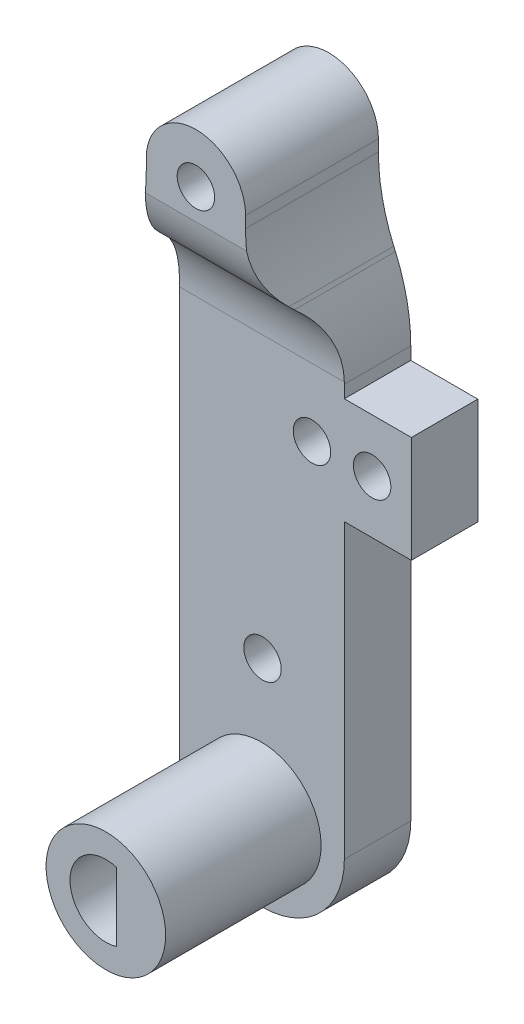
SolidWorks part; units mm, degrees
ref_plane "Front Plane" through (0, 0, 0) normal (0, 0, 1) x (1, 0, 0)
ref_plane "Top Plane" through (0, 0, 0) normal (0, 1, 0) x (1, 0, 0)
ref_plane "Right Plane" through (0, 0, 0) normal (1, 0, 0) x (0, 0, -1)
sketch "Sketch1" plane through (0, 0, 0) normal (0, 0, 1) x (1, 0, 0)
  line L0 (-5.898, 28.3342) -> (-5.898, 27.2476)
  line L1 (-2.8056, 11.5313) -> (-2.8056, 12.738)
  line L2 (3.6016, 11.5313) -> (3.6016, 1.3594)
  line L3 (-18.5662, 11.5313) -> (-18.5662, -26.5933)
  line L4 (3.6016, 1.3594) -> (-2.8056, 1.3594)
  line L5 (-2.8056, -26.5933) -> (-2.8056, 1.3594)
  line L6 (3.6016, 11.5313) -> (-2.8056, 11.5313)
  line L7 (-16.8793, 20.1661) -> (-17.0781, 19.7113)
  line L8 (-2.8056, 11.5313) -> (-18.5662, 11.5313) construction
  line L9 (-18.5662, 11.5313) -> (-18.5662, 12.5907)
  line L10 (-15.3912, 28.3342) -> (-15.3912, 27.2867)
  line L11 (-10.6859, -34.4736) -> (-36.5829, -34.4736) construction
  line L12 (-4.2728, 19.8107) -> (-4.4307, 20.1749)
  circle A0 centre (-10.6446, 28.3342) radius 1.7907
  circle A1 centre (-0.1512, 6.4513) radius 1.7907
  circle A2 centre (-5.898, 6.4513) radius 1.7907
  circle A3 centre (-10.6446, 28.3342) radius 4.7466
  circle A4 centre (-10.6859, -26.5933) radius 7.8803
  arc A5 (-18.5662, 12.5907) -> (-17.0781, 19.7113) centre (-0.7862, 12.5907) cw
  arc A6 (-15.3912, 27.2867) -> (-16.8793, 20.1661) centre (-33.1712, 27.2867) cw
  arc A7 (-5.898, 27.2476) -> (-4.4307, 20.1749) centre (11.882, 27.2476) ccw
  arc A8 (-2.8056, 12.738) -> (-4.2728, 19.8107) centre (-20.5856, 12.738) ccw
  circle A9 centre (-10.6287, -13.8687) radius 1.7907
  dimension "D1" = 17.78
  dimension "D2" = 3.5814
  dimension "D3" = 15.7606
  dimension "D4" = 3.5814
  dimension "D5" = 3.5814
  dimension "D6" = 7.9375
  dimension "D7" = 20.32
  dimension "D8" = 5.08
extrude "Boss-Extrude1" add sketch "Sketch1" along normal blind 12.7 contours A4 | L6 L8 L3 A4 L5 L4 L2 A2 A1 A9 | L8 L1 A8 L12 A7 L0 A3 L10 A6 L7 A5 L9 | A3 A0 region at (-10.6446, 23.7219, 0) region at (-9.8877, 1.7898, 0) region at (-10.6859, -26.5933, 0)
ref_plane "Plane2" through (0, -34.4736, 0) normal (0, -1, 0) x (-1, 0, 0)
sketch "Sketch5" plane through (-18.5662, 0, 0) normal (-1, 0, 0) x (0, 0, 1)
  line L0 (6.35, -34.4736) -> (12.7, -34.4736)
  line L1 (12.7, -34.4736) -> (12.7, 27.6449)
  line L2 (-6.35, -34.4736) -> (-12.7, -34.4736)
  line L3 (-12.7, -34.4736) -> (-12.7, 27.6449)
  line L4 (-6.35, 11.2679) -> (-6.35, 12.9164)
  line L5 (-12.7, 1.1079) -> (12.7, 1.1079)
  line L6 (-6.35, -34.4736) -> (-6.35, 11.2679)
  line L7 (6.35, -34.4736) -> (6.35, 11.2679)
  line L8 (6.35, 11.2679) -> (6.35, 12.9164)
  line L9 (-9.0856, 19.2772) -> (-10.0347, 20.1766)
  line L10 (9.0856, 19.2772) -> (10.0347, 20.1766)
  line L11 (12.7, -26.5933) -> (12.7, 12.5907) construction
  line L12 (-6.985, -34.4736) -> (6.985, -34.4736) construction
  line L14 (0, -26.5933) -> (0, 12.5907) construction
  arc A0 (6.35, 12.9164) -> (9.0856, 19.2772) centre (15.113, 12.9164) cw
  arc A1 (-6.35, 12.9164) -> (-9.0856, 19.2772) centre (-15.113, 12.9164) ccw
  arc A2 (12.7, 27.6449) -> (10.0347, 20.1766) centre (4.0073, 26.5374) cw
  arc A3 (-12.7, 27.6449) -> (-10.0347, 20.1766) centre (-4.0073, 26.5374) ccw
  line M2 (0, -26.5933) -> (12.7, -26.5933)
  line M3 (12.7, -26.5933) -> (12.7, 12.5907)
  line M4 (12.7, 12.5907) -> (0, 12.5907)
  dimension "D1" = 8.763
  dimension "D2" = 1.3076
  dimension "D3" = 6.35
  dimension "D4" = 12.7
  dimension "D5" = 62.1185
  dimension "D6" = 45.7414
  dimension "D7" = 1.6485
extrude "Cut-Extrude1" cut sketch "Sketch5" against normal through all contours L8 L7 L5 L1 M4 | L1 A2 L10 A0 L8 M4 | L7 L5 M2 M3 | L7 L0 L1 M2 region at (-18.5662, -30.5334, 9.525) region at (-18.5662, -12.7427, 9.525) region at (-18.5662, 6.8493, 9.525) region at (-18.5662, 16.5852, 10.1766)
sketch "Sketch6" plane through (0, 0, 6.35) normal (0, 0, 1) x (1, 0, 0)
  line L0 (-9.7271, -23.2937) -> (-9.7271, -29.8437)
  line L1 (-2.8056, -26.5933) -> (-2.8056, 1.3594) construction
  circle A0 centre (-10.7431, -26.5687) radius 5.715
  circle A1 centre (-10.7431, -26.5687) radius 3.429
  circle A2 centre (-10.6287, -13.8687) radius 1.7907 construction
  dimension "D1" = 11.43
  dimension "D2" = 6.858
  dimension "D3" = 1.016
  dimension "D4" = 12.7
  dimension "D5" = 7.9375
extrude "Boss-Extrude2" add sketch "Sketch6" along normal blind 14.859 contours A0 A1 | L0 A1 region at (-8.7251, -26.5687, 6.35) region at (-16.2964, -26.5687, 6.35)
